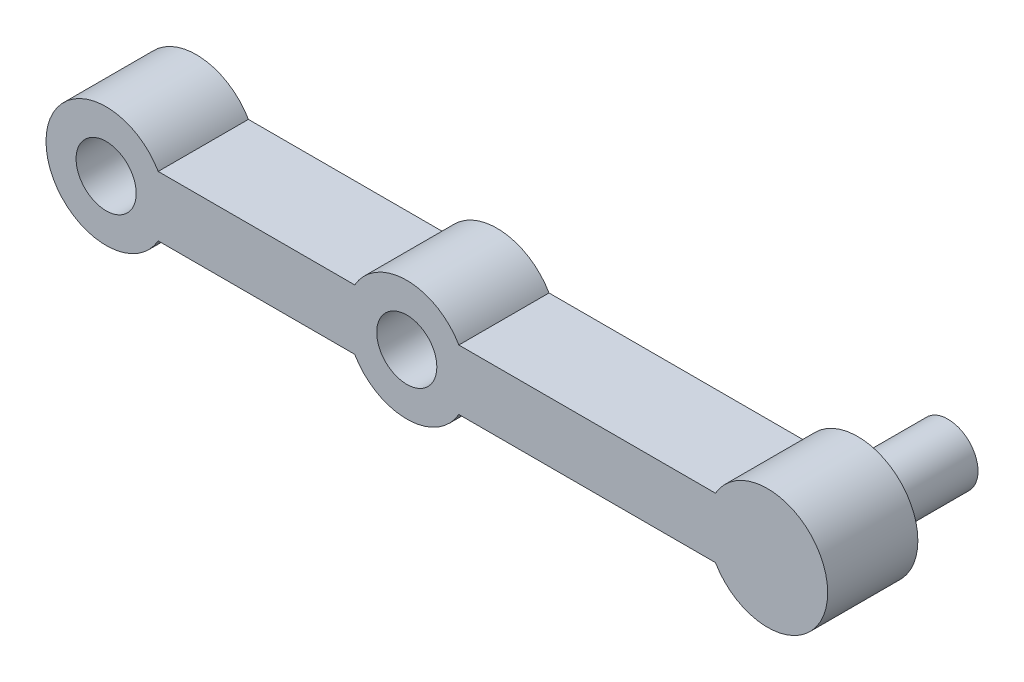
SolidWorks part; units mm, degrees
ref_plane "Спереди" through (0, 0, 0) normal (0, 0, 1) x (1, 0, 0)
ref_plane "Сверху" through (0, 0, 0) normal (0, 1, 0) x (1, 0, 0)
ref_plane "Справа" through (0, 0, 0) normal (1, 0, 0) x (0, 0, -1)
other "Configuration Table"
sketch "Sketch2" plane through (0, 0, 0) normal (0, 0, 1) x (1, 0, 0)
  line L0 (-17.3789, -4.8227) -> (-10.843, -4.8227)
  line L1 (-7.3789, -4.8227) -> (1.157, -4.8227)
  line L3 (-38.8078, -5.8227) -> (10.4516, -5.8227) construction
  line L5 (-7.3789, -6.8227) -> (1.157, -6.8227)
  line L6 (-17.3789, -6.8227) -> (-10.843, -6.8227)
  arc A3 (-17.3789, -4.8227) -> (-17.3789, -6.8227) centre (-19.1109, -5.8227) ccw
  arc A4 (-10.843, -6.8227) -> (-7.3789, -6.8227) centre (-9.1109, -5.8227) ccw
  arc A5 (1.157, -6.8227) -> (1.157, -4.8227) centre (2.8891, -5.8227) ccw
  arc A6 (-17.1109, -5.8227) -> (-17.3789, -4.8227) centre (-19.1109, -5.8227) ccw construction
  arc A7 (-17.3789, -6.8227) -> (-17.1109, -5.8227) centre (-19.1109, -5.8227) ccw construction
  arc A8 (-11.1109, -5.8227) -> (-10.843, -6.8227) centre (-9.1109, -5.8227) ccw construction
  arc A9 (-10.843, -4.8227) -> (-11.1109, -5.8227) centre (-9.1109, -5.8227) ccw construction
  arc A10 (-7.3789, -6.8227) -> (-7.1109, -5.8227) centre (-9.1109, -5.8227) ccw construction
  arc A11 (-7.3789, -4.8227) -> (-10.843, -4.8227) centre (-9.1109, -5.8227) ccw
  arc A12 (-7.1109, -5.8227) -> (-7.3789, -4.8227) centre (-9.1109, -5.8227) ccw construction
  arc A13 (1.157, -4.8227) -> (0.8891, -5.8227) centre (2.8891, -5.8227) ccw construction
  arc A14 (0.8891, -5.8227) -> (1.157, -6.8227) centre (2.8891, -5.8227) ccw construction
  dimension "D4" = 4
  dimension "D1" = 10
  dimension "D2" = 12
  dimension "D3" = 2
extrude "Boss-Extrude1" add sketch "Sketch2" along normal blind 3 contours L1 A11 L0 A3 L6 A4 L5 A5 region at (-8.1849, -5.8227, 0)
ref_plane "Plane1" through (0, 0, 3) normal (0, 0, 1) x (1, 0, 0)
sketch "Sketch3" plane through (0, 0, 3) normal (0, 0, 1) x (1, 0, 0)
  circle A0 centre (-9.1109, -5.8227) radius 1
  circle A1 centre (-19.1109, -5.8227) radius 1
  dimension "D1" = 2
extrude "Cut-Extrude1" cut sketch "Sketch3" against normal up to surface (3 mm away) contours A0 | A1 region at (-9.1109, -5.8227, 3) up to face at (-8.6109, -5.8227, 0)
ref_plane "Plane2" through (0, 0, 0) normal (0, 0, -1) x (-1, 0, 0)
sketch "Sketch4" plane through (0, 0, 0) normal (0, 0, -1) x (-1, 0, 0)
  circle A0 centre (-2.8891, -5.8227) radius 1
  circle A2 centre (9.1109, -5.8227) radius 1 construction
extrude "Boss-Extrude2" add sketch "Sketch4" along normal blind 3 contours A0
equation "\"R small\"= 2"
equation "\"R big\"= 4"
equation "\"width\"= 0.6"
equation "\"border width\"= 1"
equation "\"D4@Sketch2\"=\"R big\""
equation "\"D3@Sketch2\"=\"R small\""
equation "\"D1@Sketch3\"=\"R small\""
